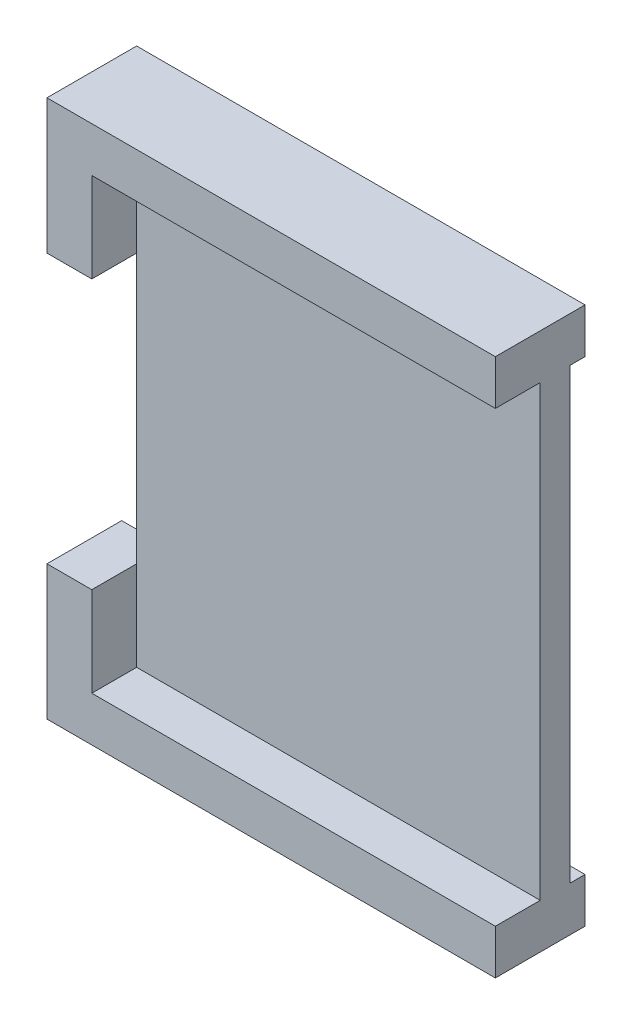
SolidWorks part; units mm, degrees
ref_plane "Front Plane" through (0, 0, 0) normal (0, 0, 1) x (1, 0, 0)
ref_plane "Top Plane" through (0, 0, 0) normal (0, 1, 0) x (1, 0, 0)
ref_plane "Right Plane" through (0, 0, 0) normal (1, 0, 0) x (0, 0, -1)
sketch "Sketch1" plane through (0, 0, 0) normal (0, 0, 1) x (1, 0, 0)
  line L0 (-12, 9) -> (-12, -9)
  line L1 (15, 15) -> (-15, 15)
  line L2 (15, 15) -> (15, -15)
  line L3 (15, -15) -> (-15, -15)
  line L4 (-15, 15) -> (-15, -15)
  line L5 (15, 15) -> (-15, -15) construction
  line L6 (15, -15) -> (-15, 15) construction
  line L7 (-15, 15) -> (-12, 15)
  line L8 (-15, 15) -> (-15, 9)
  line L9 (-15, 9) -> (-12, 9)
  line L10 (-12, 15) -> (-12, 9)
  line L11 (-15, -15) -> (-12, -15)
  line L12 (-15, -15) -> (-15, -9)
  line L13 (-15, -9) -> (-12, -9)
  line L14 (-12, -15) -> (-12, -9)
  line L16 (-15, -15) -> (15, -15)
  line L17 (-15, -15) -> (-15, -18)
  line L18 (-15, -18) -> (15, -18)
  line L19 (15, -15) -> (15, -18)
  line L20 (15, 15) -> (-15, 15)
  line L21 (15, 15) -> (15, 18)
  line L22 (15, 18) -> (-15, 18)
  line L23 (-15, 15) -> (-15, 18)
  point P0 (0, 0)
  dimension "D1" = 18
  dimension "D2" = 30
  dimension "D3" = 30
  dimension "D4" = 3
extrude "Boss-Extrude1" add sketch "Sketch1" along normal blind 2 contours L14 L3 L2 L1 L10 L0 | L10 L1 L4 L9 | L3 L14 L13 L4 | L23 L1 L21 L22 | L19 L3 L17 L18 region at (1.5, 0, 0) region at (-13.5, 12, 0) region at (-13.5, -12, 0) region at (0, 16.5, 0) region at (0, -16.5, 0)
extrude "Boss-Extrude2" add sketch "Sketch1<3>" along normal blind 5 contours L10 L1 L4 L9 | L23 L1 L21 L22 | L3 L14 L13 L4 | L19 L3 L17 L18 region at (-13.5, 12, 0) region at (-13.5, -12, 0) region at (0, 16.5, 0) region at (0, -16.5, 0)
sketch "Sketch1<3>" plane through (0, 0, 0) normal (0, 0, 1) x (1, 0, 0) same geometry as "Sketch1"
extrude "Boss-Extrude3" add sketch "Sketch1<4>" against normal blind 1 contours L19 L3 L17 L18 | L23 L1 L21 L22 region at (0, 16.5, 0) region at (0, -16.5, 0)
sketch "Sketch1<4>" plane through (0, 0, 0) normal (0, 0, 1) x (1, 0, 0) same geometry as "Sketch1"
